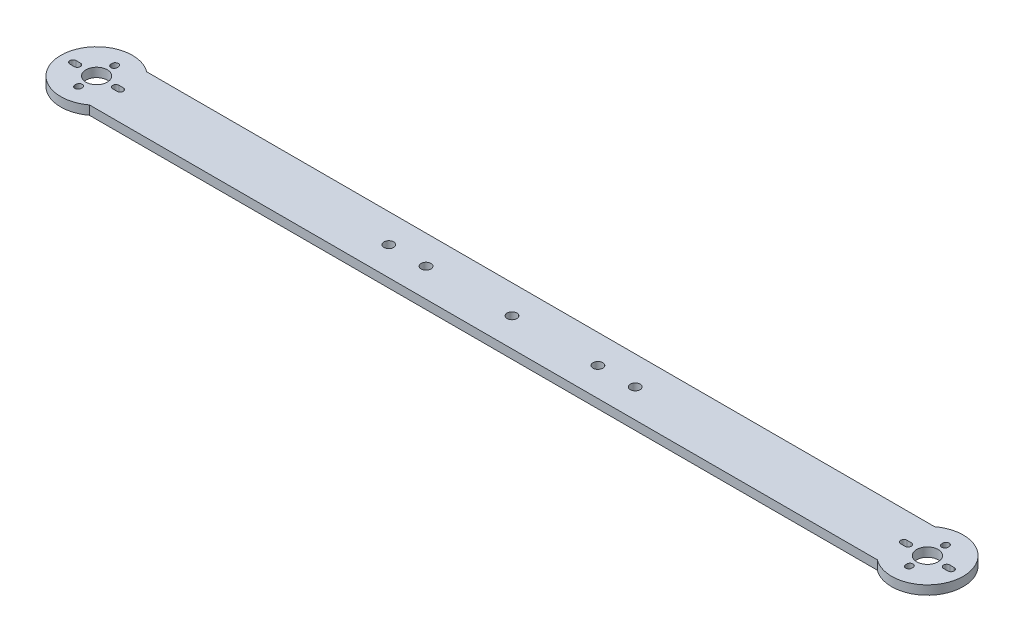
SolidWorks part; units mm, degrees
material "Thornel Mat VMA"
ref_plane "Front Plane" through (0, 0, 0) normal (0, 0, 1) x (1, 0, 0)
ref_plane "Top Plane" through (0, 0, 0) normal (0, 1, 0) x (1, 0, 0)
ref_plane "Right Plane" through (0, 0, 0) normal (1, 0, 0) x (0, 0, -1)
sketch "Sketch1" plane through (0, 0, 0) normal (0, 1, 0) x (1, 0, 0)
  line L0 (0, 12.7) -> (0, -12.7) construction
  line L1 (-174.625, 12.7) -> (174.625, 12.7)
  line L3 (-174.625, -12.7) -> (174.625, -12.7)
  arc A0 (-174.625, 12.7) -> (-174.625, -12.7) centre (-184.15, 0) ccw
  arc A1 (174.625, -12.7) -> (174.625, 12.7) centre (184.15, 0) ccw
  point P8 (0, 12.7)
  point P12 (0, 0)
  dimension "D3" = 31.75
  dimension "D4" = 31.75
extrude "Boss-Extrude1" add sketch "Sketch1" along normal blind 4
sketch "Sketch2" plane through (0, 4, 0) normal (0, 1, 0) x (1, 0, 0)
  line L0 (173.6914, 0) -> (175.6086, 0) construction
  line L1 (173.6914, 1.375) -> (175.6086, 1.375)
  line L2 (173.6914, -1.375) -> (175.6086, -1.375)
  line L3 (184.15, 0) -> (184.15, 3.2374) construction
  line L4 (194.6086, 0) -> (192.6914, 0) construction
  line L5 (194.6086, 1.375) -> (192.6914, 1.375)
  line L6 (194.6086, -1.375) -> (192.6914, -1.375)
  line L7 (184.15, 8.25) -> (184.15, 7.75) construction
  line L8 (185.525, 8.25) -> (185.525, 7.75)
  line L9 (182.775, 8.25) -> (182.775, 7.75)
  line L10 (184.15, -8.25) -> (184.15, -7.75) construction
  line L11 (185.525, -8.25) -> (185.525, -7.75)
  line L12 (182.775, -8.25) -> (182.775, -7.75)
  line L13 (0, 0) -> (184.15, 0) construction
  line L14 (0, 0) -> (0, 12.7) construction
  line L15 (174.625, 12.7) -> (-174.625, 12.7) construction
  line L16 (-184.15, 0) -> (-184.15, 3.2374) construction
  line L17 (-184.15, -8.25) -> (-184.15, -7.75) construction
  line L18 (-185.525, -8.25) -> (-185.525, -7.75)
  line L19 (-182.775, -8.25) -> (-182.775, -7.75)
  line L20 (-184.15, 8.25) -> (-184.15, 7.75) construction
  line L21 (-185.525, 8.25) -> (-185.525, 7.75)
  line L22 (-182.775, 8.25) -> (-182.775, 7.75)
  line L23 (-194.6086, 0) -> (-192.6914, 0) construction
  line L24 (-194.6086, 1.375) -> (-192.6914, 1.375)
  line L25 (-194.6086, -1.375) -> (-192.6914, -1.375)
  line L26 (-173.6914, 0) -> (-175.6086, 0) construction
  line L27 (-173.6914, 1.375) -> (-175.6086, 1.375)
  line L28 (-173.6914, -1.375) -> (-175.6086, -1.375)
  line L29 (184.15, -8) -> (184.15, 8) construction
  circle A0 centre (184.15, 0) radius 4.75
  arc A1 (173.6914, 1.375) -> (173.6914, -1.375) centre (173.6914, 0) ccw
  arc A2 (175.6086, -1.375) -> (175.6086, 1.375) centre (175.6086, 0) ccw
  arc A3 (194.6086, 1.375) -> (194.6086, -1.375) centre (194.6086, 0) cw
  arc A4 (192.6914, -1.375) -> (192.6914, 1.375) centre (192.6914, 0) cw
  arc A5 (185.525, 8.25) -> (182.775, 8.25) centre (184.15, 8.25) ccw
  arc A6 (182.775, 7.75) -> (185.525, 7.75) centre (184.15, 7.75) ccw
  arc A7 (185.525, -8.25) -> (182.775, -8.25) centre (184.15, -8.25) cw
  arc A8 (182.775, -7.75) -> (185.525, -7.75) centre (184.15, -7.75) cw
  circle A9 centre (-184.15, 0) radius 4.75
  arc A10 (-185.525, -8.25) -> (-182.775, -8.25) centre (-184.15, -8.25) ccw
  arc A11 (-182.775, -7.75) -> (-185.525, -7.75) centre (-184.15, -7.75) ccw
  arc A12 (-185.525, 8.25) -> (-182.775, 8.25) centre (-184.15, 8.25) cw
  arc A13 (-182.775, 7.75) -> (-185.525, 7.75) centre (-184.15, 7.75) cw
  arc A14 (-194.6086, 1.375) -> (-194.6086, -1.375) centre (-194.6086, 0) ccw
  arc A15 (-192.6914, -1.375) -> (-192.6914, 1.375) centre (-192.6914, 0) ccw
  arc A16 (-173.6914, 1.375) -> (-173.6914, -1.375) centre (-173.6914, 0) cw
  arc A17 (-175.6086, -1.375) -> (-175.6086, 1.375) centre (-175.6086, 0) cw
  point P4 (174.65, 0)
  point P12 (193.65, 0)
  point P19 (184.15, 8)
  point P26 (184.15, -8)
  point P41 (-184.15, -8)
  point P48 (-184.15, 8)
  point P55 (-193.65, 0)
  point P62 (-174.65, 0)
  point P69 (184.15, 0)
  dimension "D4" = 9.5
  dimension "D1" = 16
  dimension "D2" = 19
  dimension "D3" = 184.15
  dimension "D5" = 0.5
extrude "Cut-Extrude1" cut sketch "Sketch2" against normal through all
sketch "Sketch3" plane through (0, 4, 0) normal (0, 1, 0) x (1, 0, 0)
  circle A0 centre (0, 0) radius 2.159
  circle A1 centre (38.1, 0) radius 2.159
  circle A2 centre (-38.1, 0) radius 2.159
  dimension "D1" = 38.1
  dimension "D3" = 4.318
  dimension "D4" = 4.318
  dimension "D5" = 4.318
  dimension "D2" = 38.1
extrude "Cut-Extrude2" cut sketch "Sketch3" against normal through all
sketch "Sketch4" plane through (0, 4, 0) normal (0, 1, 0) x (1, 0, 0)
  line L0 (0, 12.7) -> (0, -33.8789) construction
  line L1 (174.625, 12.7) -> (-174.625, 12.7) construction
  circle A0 centre (54.61, 0) radius 2.159
  circle A1 centre (184.15, 0) radius 4.75 construction
  circle A2 centre (-54.61, 0) radius 2.159
  dimension "D1" = 4.318
  dimension "D2" = 129.54
extrude "Cut-Extrude3" cut sketch "Sketch4" against normal through all
